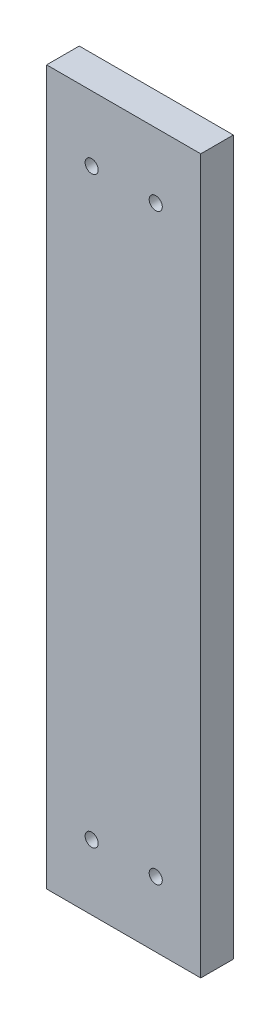
SolidWorks part; units mm, degrees
ref_plane "Front Plane" through (0, 0, 0) normal (0, 0, 1) x (1, 0, 0)
ref_plane "Top Plane" through (0, 0, 0) normal (0, 1, 0) x (1, 0, 0)
ref_plane "Right Plane" through (0, 0, 0) normal (1, 0, 0) x (0, 0, -1)
sketch "Sketch1" plane through (0, 0, 0) normal (0, 1, 0) x (1, 0, 0)
  line L1 (0, 0) -> (60, 0)
  line L2 (0, 0) -> (0, 12.7)
  line L3 (0, 12.7) -> (60, 12.7)
  line L4 (60, 0) -> (60, 12.7)
  dimension "D1" = 60
  dimension "D2" = 12.7
extrude "Boss-Extrude1" add sketch "Sketch1" along normal blind 277.876
sketch "Sketch2" plane through (0, 0, 0) normal (0, 0, 1) x (1, 0, 0)
  line L0 (0, 138.938) -> (60, 138.938) construction
  line L1 (0, 277.876) -> (0, 0) construction
  line L2 (60, 277.876) -> (60, 0) construction
  line L3 (0, 277.876) -> (60, 277.876) construction
  point P0 (17.526, 252.476)
  point P1 (42.474, 252.476)
  point P10 (42.474, 25.4)
  point P11 (17.526, 25.4)
  dimension "D1" = 25.4
  dimension "D2" = 25.4
  dimension "D3" = 17.526
  dimension "D4" = 17.526
hole_wizard "1/4-20 Tapped Hole1" positions "3DSketch1" profile "Sketch3" tap size "1/4-20" standard "ANSI Inch" end condition through all
sketch3d "3DSketch1"
  point P0 (17.526, 252.476, 0)
  point P3 (42.474, 252.476, 0)
  point P6 (17.526, 25.4, 0)
  point P9 (42.474, 25.4, 0)
sketch "Sketch3" plane through (17.526, 252.476, 0) normal (1, 0, 0) x (0, -1, 0)
  line L0 (0, 0) -> (0, 12.7)
  line L1 (0, 12.7) -> (2.5527, 12.7)
  line L2 (2.5527, 12.7) -> (2.5527, 0)
  line L5 (2.5527, 0) -> (0, 0)
  line L11 (0, -6.35) -> (0, 107.95) construction
  dimension "Thru Tap Drill Dia." = 5.1054
  dimension "Thru Tap Drill Depth" = 12.7
cosmetic thread "Hole Thread1"
cosmetic thread "Hole Thread2"
cosmetic thread "Hole Thread3"
cosmetic thread "Hole Thread4"
